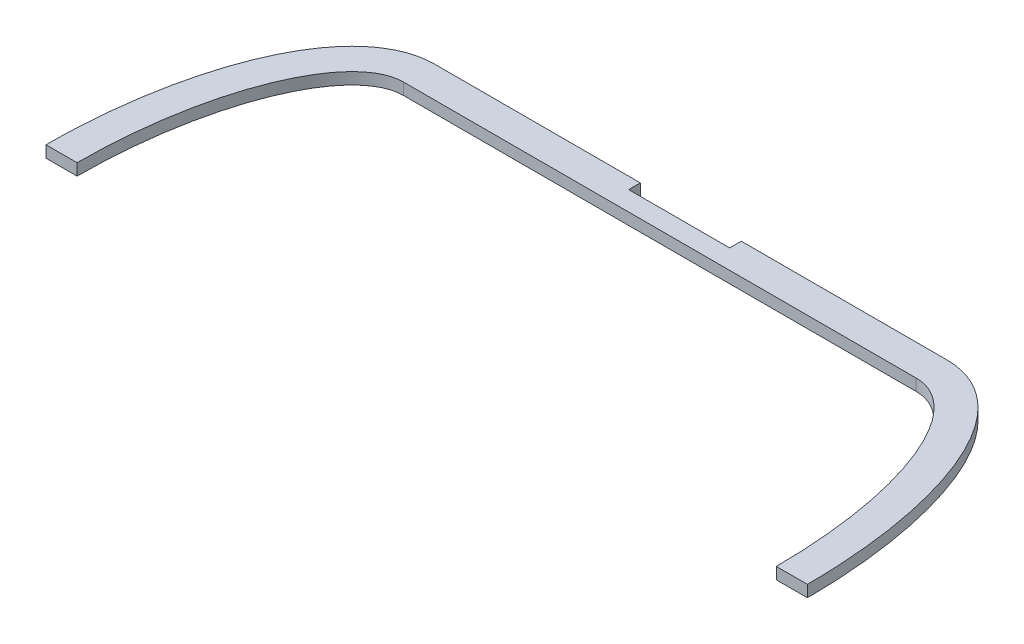
SolidWorks part; units mm, degrees
ref_plane "Front Plane" through (0, 0, 0) normal (0, 0, 1) x (1, 0, 0)
ref_plane "Top Plane" through (0, 0, 0) normal (0, 1, 0) x (1, 0, 0)
ref_plane "Right Plane" through (0, 0, 0) normal (1, 0, 0) x (0, 0, -1)
sketch "Sketch1" plane through (0, 0, 0) normal (0, 1, 0) x (1, 0, 0)
  line L0 (33, 30) -> (-33, -30) construction
  line L1 (-33, 30) -> (33, 30)
  line L2 (-33, 30) -> (-33, -30) construction
  line L3 (-33, -30) -> (33, -30)
  line L4 (33, 30) -> (33, -30) construction
  line L5 (-33, 30) -> (33, -30) construction
  line L6 (0, 30) -> (0, -30) construction
  ellipse E0 centre (-33, 0) end of major axis (-33, -30) minor radius 12 (-33, 30) -> (-33, -30) ccw
  ellipse E1 centre (33, 0) end of major axis (33, 30) minor radius 12 (33, 30) -> (33, -30) cw
  point P20 (0, 0)
  dimension "D1" = 66
  dimension "D2" = 60
  dimension "D3" = 12
extrude "Boss-Extrude1" add sketch "Sketch1" along normal blind 1.5 contours L1 E1 L3 E0
shell "Shell1" thickness 4 removed face at (0, 0, 0) removed face at (0, 1.5, 0) outward yes
sketch "Sketch2" plane through (0, 0, 0) normal (0, 1, 0) x (1, 0, 0)
  line L1 (-53.1803, 0) -> (55.7581, 0)
  line L2 (-53.1803, 0) -> (-53.1803, -37.45)
  line L3 (-53.1803, -37.45) -> (55.7581, -37.45)
  line L4 (55.7581, 0) -> (55.7581, -37.45)
extrude "Cut-Extrude2" cut sketch "Sketch2" along normal through all
sketch "Sketch3" plane through (0, 1.5, 0) normal (0, 1, 0) x (1, 0, 0)
  line L0 (-33, 30) -> (33, 30) construction
  line L1 (6.5, 32.5) -> (-6.5, 32.5)
  line L3 (6.5, 44.9992) -> (-6.5, 44.9992)
  line L4 (-6.5, 32.5) -> (-6.5, 44.9992)
  line L5 (0, -29.1144) -> (0, 21.9505) construction
  line L6 (6.5, 32.5) -> (6.5, 44.9992)
  dimension "D1" = 2.5
extrude "Cut-Extrude3" cut sketch "Sketch3" against normal through all
